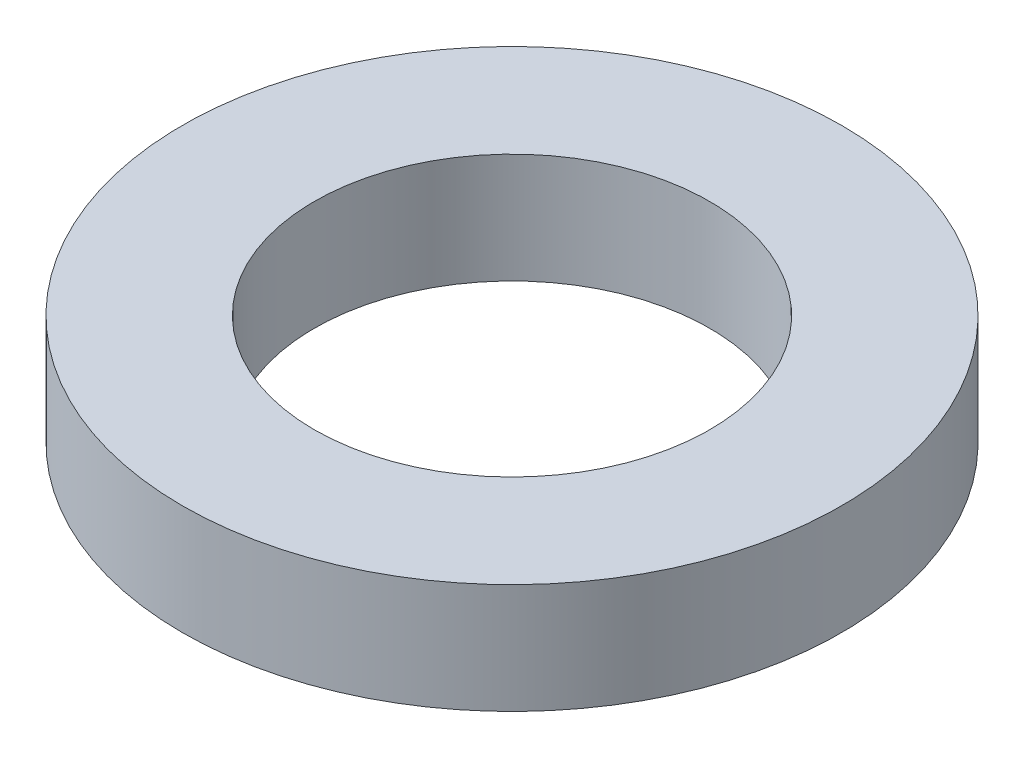
SolidWorks part; units mm, degrees
ref_plane "Front Plane" through (0, 0, 0) normal (0, 0, 1) x (1, 0, 0)
ref_plane "Top Plane" through (0, 0, 0) normal (0, 1, 0) x (1, 0, 0)
ref_plane "Right Plane" through (0, 0, 0) normal (1, 0, 0) x (0, 0, -1)
sketch "Sketch1" plane through (0, 0, 0) normal (0, 1, 0) x (1, 0, 0)
  circle A0 centre (0, 0) radius 75
  dimension "FLANGE_OD" = 150
extrude "Boss-Extrude1" add sketch "Sketch1" along normal blind 25
sketch "Sketch2" plane through (0, 0, 0) normal (0, 1, 0) x (1, 0, 0)
  circle A0 centre (0, 0) radius 45
  dimension "BORE_D" = 90
extrude "Cut-Extrude1" cut sketch "Sketch2" along normal through all
sketch "Sketch3" plane through (0, 25, 0) normal (0, 1, 0) x (1, 0, 0)
  circle A0 centre (0, 0) radius 34.434 construction
  circle A1 centre (-34.434, 0) radius 4.3486
  dimension "BOLT_D" = 8.6972
  dimension "BOLT_PCD" = 68.868
extrude "Cut-Extrude2" cut sketch "Sketch3" against normal blind 24.2562 rebuild error yes
pattern_circular "CirPattern1" count 8 over 360 rebuild error yes
